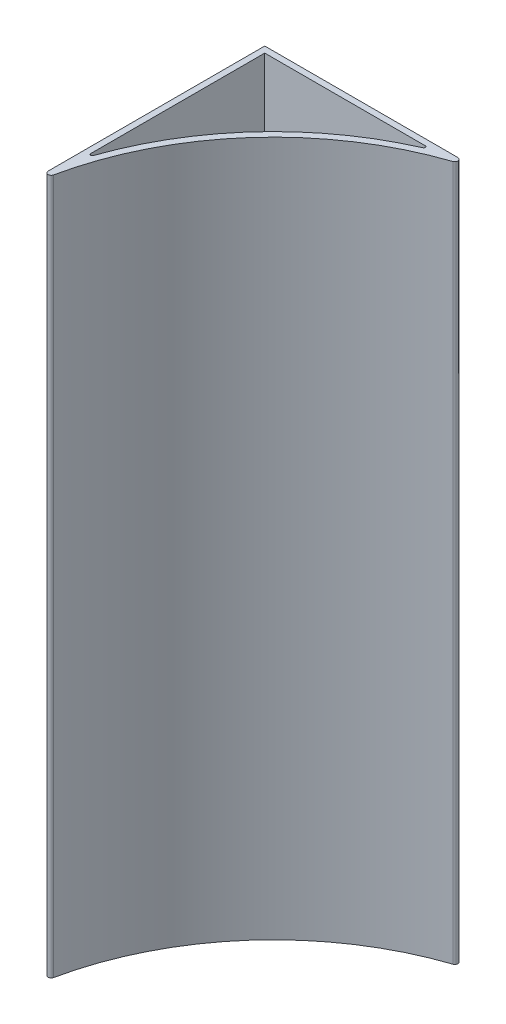
SolidWorks part; units mm, degrees
ref_plane "Front Plane" through (0, 0, 0) normal (1, 0, 0) x (0, 1, 0)
ref_plane "Top Plane" through (0, 0, 0) normal (0, 0, 1) x (0, 1, 0)
ref_plane "Right Plane" through (0, 0, 0) normal (0, 1, 0) x (-1, 0, 0)
sketch "Sketch2" plane through (0, 0, 0) normal (0, 1, 0) x (-1, 0, 0)
  line L0 (6.9449, 0) -> (70, 0)
  line L1 (70, 0) -> (70, 70.7275)
  line L3 (68, 58.8563) -> (68, 2)
  line L5 (68, 2) -> (15.5888, 2)
  arc A0 (68.0213, 70.9329) -> (6.6274, 1.9482) centre (-22.8571, 90) cw
  arc A1 (70, 70.7275) -> (68.0213, 70.9329) centre (69, 70.7275) ccw
  arc A4 (15.3877, 2.9578) -> (67.0273, 59.0192) centre (-22.8571, 90) ccw
  arc A5 (67.0273, 59.0192) -> (68, 58.8563) centre (67.5, 58.8563) cw
  arc A6 (15.3877, 2.9578) -> (15.5888, 2) centre (15.5888, 2.5) ccw
  arc A7 (6.9449, 0) -> (6.6274, 1.9482) centre (6.9449, 1) cw
  point P7 (70, 90)
  point P14 (68, 62)
  point P18 (0, 0)
  dimension "D3" = 1
  dimension "D4" = 60
  dimension "D6" = 2
  dimension "D7" = 0.5
  dimension "D8" = 1
  dimension "D1" = 70
  dimension "D2" = 90
  dimension "D5" = 2
extrude "Boss-Extrude1" add sketch "Sketch2" along normal blind 113.5 and the other way blind 113.5
sketch "Sketch3" plane through (0, 0, 0) normal (0, 0, -1) x (1, 0, 0)
  line L0 (-1000, 0) -> (49000, 0) construction
  line L2 (-39.9, -69.8) -> (-30.1, -69.8)
  line L3 (-39.9, -69.8) -> (-39.9, -50)
  line L4 (-39.9, -50) -> (-30.1, -50)
  line L5 (-30.1, -69.8) -> (-30.1, -50)
  line L6 (-39.9, -69.8) -> (-30.1, -50) construction
  line L7 (-39.9, -50) -> (-30.1, -69.8) construction
  line L8 (-35, -1113.5) -> (-35, 48886.5) construction
  line L9 (-39.9, 50) -> (-30.1, 69.8) construction
  line L10 (-39.9, 69.8) -> (-30.1, 50) construction
  line L11 (-30.1, 69.8) -> (-30.1, 50)
  line L12 (-39.9, 50) -> (-30.1, 50)
  line L13 (-39.9, 69.8) -> (-39.9, 50)
  line L14 (-39.9, 69.8) -> (-30.1, 69.8)
  line L15 (-1025, -150) -> (48975, -150) construction
  point P1 (-35, -59.9)
  point P17 (-35, 59.9)
  dimension "D1" = 19.8
  dimension "D2" = 9.8
  dimension "D3" = 150
  dimension "D4" = 100
  dimension "D5" = 35
extrude "Cut-Extrude1" cut sketch "Sketch3" against normal blind 5
